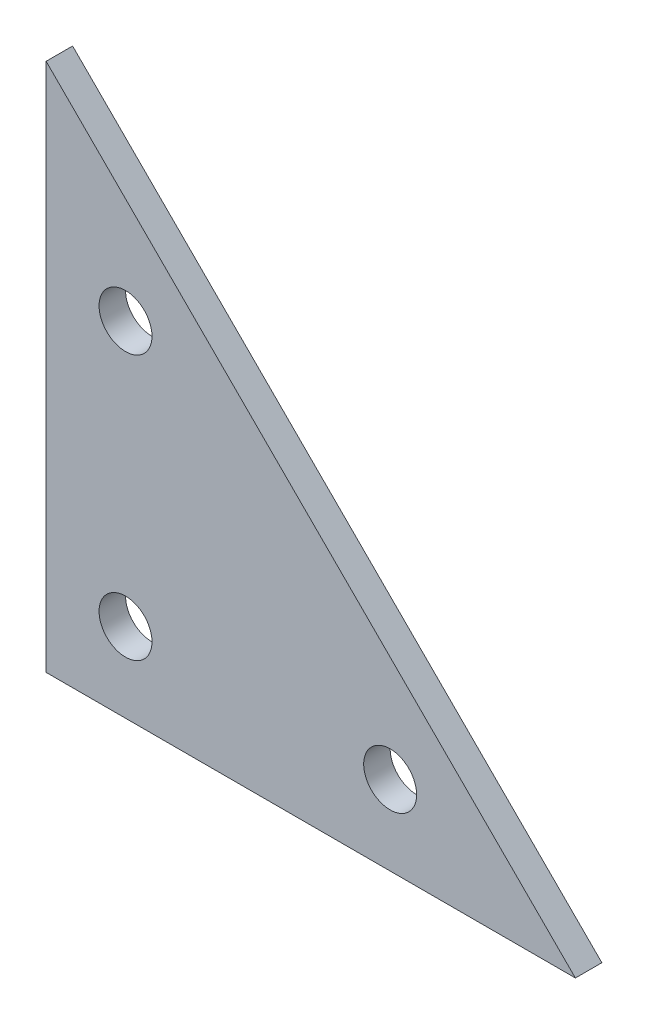
SolidWorks part; units mm, degrees
ref_plane "Front Plane" through (0, 0, 0) normal (0, 0, 1) x (1, 0, 0)
ref_plane "Top Plane" through (0, 0, 0) normal (0, 1, 0) x (1, 0, 0)
ref_plane "Right Plane" through (0, 0, 0) normal (1, 0, 0) x (0, 0, -1)
sketch "Sketch1" plane through (0, 0, 0) normal (0, 0, 1) x (1, 0, 0)
  line L0 (0, 0) -> (100, 0)
  line L1 (100, 0) -> (0, 100)
  line L2 (0, 100) -> (0, 0)
  dimension "D1" = 100
  dimension "D2" = 100
extrude "Boss-Extrude1" add sketch "Sketch1" along normal blind 5
sketch "Sketch2" plane through (0, 0, 5) normal (0, 0, 1) x (1, 0, 0)
  line L0 (0, 100) -> (0, 0) construction
  line L1 (0, 0) -> (100, 0) construction
  circle A0 centre (15, 65) radius 5
  circle A1 centre (15, 15) radius 5
  circle A2 centre (65, 15) radius 5
  dimension "D1" = 10
  dimension "D2" = 10
  dimension "D3" = 10
  dimension "D4" = 15
  dimension "D5" = 15
  dimension "D6" = 50
  dimension "D7" = 50
extrude "Cut-Extrude1" cut sketch "Sketch2" against normal blind 20
